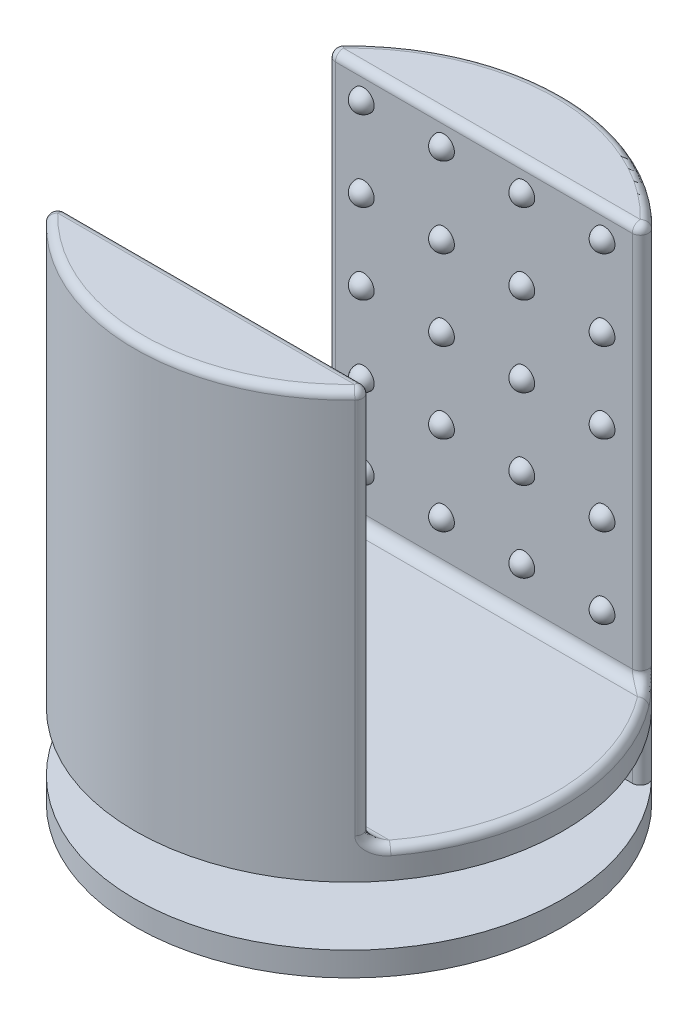
SolidWorks part; units mm, degrees
ref_plane "Front Plane" through (0, 0, 0) normal (0, 0, 1) x (1, 0, 0)
ref_plane "Top Plane" through (0, 0, 0) normal (0, 1, 0) x (1, 0, 0)
ref_plane "Right Plane" through (0, 0, 0) normal (1, 0, 0) x (0, 0, -1)
ref_plane "Plane1" through (-3.75, 0, 0) normal (1, 0, 0) x (0, 0, -1)
sketch "Sketch2" plane through (0, 0, 0) normal (0, 1, 0) x (1, 0, 0)
  line L1 (-35, 12.5) -> (35, 12.5)
  line L2 (-35, 12.5) -> (-35, -12.5)
  line L3 (-35, -12.5) -> (35, -12.5)
  line L4 (35, 12.5) -> (35, -12.5)
  line L5 (-35, 12.5) -> (35, -12.5) construction
  line L6 (-35, -12.5) -> (35, 12.5) construction
  point P0 (0, 0)
  dimension "D1" = 25
  dimension "D2" = 70
sketch "Sketch3" plane through (0, 0, 0) normal (0, 1, 0) x (1, 0, 0)
  circle A0 centre (0, 0) radius 20
  dimension "D1" = 40
extrude "Boss-Extrude1" add sketch "Sketch3" along normal blind 40
sketch "Sketch4" plane through (0, 40, 0) normal (0, 1, 0) x (1, 0, 0)
  line L8 (-35.1, 12.6) -> (-35.1, -12.6)
  line L9 (35.1, 12.6) -> (-35.1, 12.6)
  line L10 (35.1, -12.6) -> (35.1, 12.6)
  line L11 (-35.1, -12.6) -> (35.1, -12.6)
  line L12 (-35.1, 12.6) -> (-35.1, -12.6)
  line L13 (35.1, 12.6) -> (-35.1, 12.6)
  line L14 (35.1, -12.6) -> (35.1, 12.6)
  line L15 (-35.1, -12.6) -> (35.1, -12.6)
  dimension "D1" = 0.1
extrude "Cut-Extrude1" cut sketch "Sketch4" against normal offset from surface (37 mm away) 3 up to face at (0, 0, 20)
sketch "Sketch5" plane through (-3.75, 0, 0) normal (1, 0, 0) x (0, 0, -1)
  line L0 (-12.6, 40) -> (-12.6, 3) construction
  line L1 (-12.6, 40) -> (-12.6, 3) construction
  line L2 (-11.6, 37.5) -> (-13.6, 37.5) construction
  line L3 (-11.6, 37.5) -> (-13.6, 37.5)
  arc A0 (-11.6, 37.5) -> (-13.6, 37.5) centre (-12.6, 37.5) ccw
  point P4 (-12.6, 37.5)
  dimension "D1" = 2.5
  dimension "D2" = 2
revolve "Revolve1" add sketch "Sketch5" angle 360 about L3
pattern_linear "LPattern1" count 3 spacing 7.5 along (1, 0, 0) count 2 spacing 7.5 along (-1, 0, 0) of "Revolve1" pattern seed only yes
pattern_linear "LPattern2" count 5 spacing 7.5 along (0, -1, 0) of "LPattern1"
mirror "Mirror1" about plane through (0, 0, 0) normal (0, 0, 1) of "LPattern2", "LPattern1"
fillet "Fillet3" radius 1 2 edges at (0, 3, 12.6) (0, 3, -12.6)
fillet "Fillet4" radius 0.75 10 edges at (15.6511, 3.4759, -12.4517) (20, 3, 0) (15.7314, 3.3386, 12.35) (-15.7314, 3.3386, -12.35) (-20, 3, 0) (-15.6511, 3.4759, 12.4517) (15.5319, 22, -12.6) (-15.5319, 22, -12.6) (15.5319, 22, 12.6) (-15.5319, 22, 12.6)
fillet "Fillet5" radius 0.75 8 edges at (-14.5588, 40, 13.0564) (0, 40, 12.6) (14.5588, 40, 13.0564) (0, 40, 20) (-14.5588, 40, -13.0564) (0, 40, -20) (14.5588, 40, -13.0564) (0, 40, -12.6)
sketch "Sketch6" plane through (0, 0, 0) normal (0, -1, 0) x (1, 0, 0)
  circle A1 centre (0, 0) radius 20
  circle A2 centre (0, 0) radius 20
  dimension "D1" = 0
extrude "Boss-Extrude2" add sketch "Sketch6" along normal blind 7.5
sketch "Sketch7" plane through (0, 0, 0) normal (0, 0, 1) x (1, 0, 0)
  line L1 (-20, -5.25) -> (20, -5.25)
  line L2 (-20, -5.25) -> (-20, 0.25)
  line L3 (-20, 0.25) -> (20, 0.25)
  line L4 (20, -5.25) -> (20, 0.25)
  line L5 (-20, -5.25) -> (20, 0.25) construction
  line L6 (-20, 0.25) -> (20, -5.25) construction
  line L11 (-15.9609, 2.25) -> (-20, 2.25) construction
  point P0 (0, -2.5)
  point P5 (0, -6.5072)
  point P15 (0, 1.5)
  dimension "D1" = 5.5
  dimension "D2" = 2
  dimension "D3" = 40
extrude "Cut-Extrude2" cut sketch "Sketch7" against normal up to vertex (-12.6 mm away) and the other way through all up to point (-13.8687, 4, 12.6)
sketch "Sketch8" plane through (0, -7.5, 0) normal (0, -1, 0) x (1, 0, 0)
  line L1 (9.75, 15) -> (-9.75, 15)
  line L2 (9.75, 15) -> (9.75, -15)
  line L3 (9.75, -15) -> (-9.75, -15)
  line L4 (-9.75, 15) -> (-9.75, -15)
  line L5 (9.75, 15) -> (-9.75, -15) construction
  line L6 (9.75, -15) -> (-9.75, 15) construction
  point P0 (0, 0)
  dimension "D1" = 19.5
  dimension "D2" = 30
extrude "Cut-Extrude3" cut sketch "Sketch8" against normal blind 0.75
fillet "Fillet7" radius 0.75 2 edges at (-15.5319, -2.5, -12.6) (15.5319, -2.5, -12.6)
